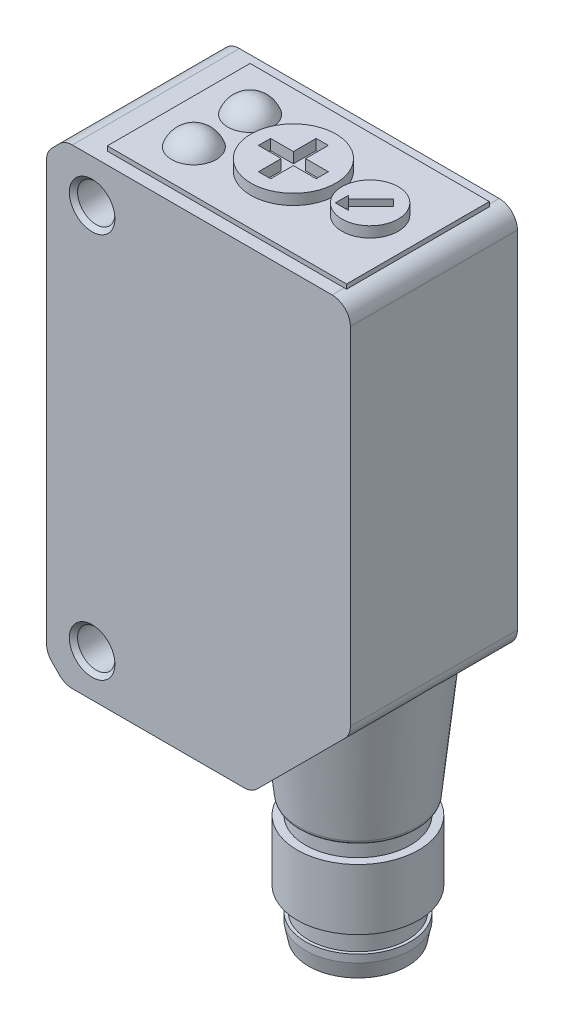
SolidWorks part; units mm, degrees
ref_plane "Front Plane" through (0, 0, 0) normal (0, 0, 1) x (1, 0, 0)
ref_plane "Top Plane" through (0, 0, 0) normal (0, 1, 0) x (1, 0, 0)
ref_plane "Right Plane" through (0, 0, 0) normal (1, 0, 0) x (0, 0, -1)
ref_plane "Plane1" through (0, 0, 0) normal (0, 0, 1) x (1, 0, 0)
sketch "Sketch1" plane through (0, 0, 0) normal (0, 0, 1) x (1, 0, 0)
  line L0 (-3, 26.5029) -> (-3, -1.1029)
  line L1 (-2.6485, -1.9515) -> (-2.1515, -2.4485)
  line L2 (-1.3029, -2.8) -> (10.0029, -2.8)
  line L3 (10.8515, -2.4485) -> (16.6485, 3.3485)
  line L4 (17, 4.1971) -> (17, 27)
  line L5 (15.8, 28.2) -> (-1.3029, 28.2)
  line L6 (-2.1515, 27.8485) -> (-2.6485, 27.3515)
  arc A0 (-3, -1.1029) -> (-2.6485, -1.9515) centre (-1.8, -1.1029) ccw
  arc A1 (-2.1515, -2.4485) -> (-1.3029, -2.8) centre (-1.3029, -1.6) ccw
  arc A2 (10.0029, -2.8) -> (10.8515, -2.4485) centre (10.0029, -1.6) ccw
  arc A3 (16.6485, 3.3485) -> (17, 4.1971) centre (15.8, 4.1971) ccw
  arc A4 (17, 27) -> (15.8, 28.2) centre (15.8, 27) ccw
  arc A5 (-1.3029, 28.2) -> (-2.1515, 27.8485) centre (-1.3029, 27) ccw
  arc A6 (-2.6485, 27.3515) -> (-3, 26.5029) centre (-1.8, 26.5029) ccw
extrude "Boss-Extrude1" add sketch "Sketch1" against normal blind 11
ref_plane "Plane2" through (0, 0, -5.5) normal (0, 0, 1) x (1, 0, 0)
sketch "Sketch2" plane through (0, 0, -5.5) normal (0, 0, 1) x (1, 0, 0)
  line L0 (12, 4.7) -> (16.8991, 4.7)
  line L1 (16.8991, 4.7) -> (15.8973, -4.8314)
  line L2 (15.599, -5.1) -> (15.45, -5.1)
  line L3 (15.45, -5.1) -> (15.45, -6.1)
  line L4 (15.45, -6.1) -> (16, -6.1)
  line L5 (16, -6.1) -> (16, -10.1)
  line L6 (16, -10.1) -> (15.25, -10.1)
  line L7 (15.25, -10.1) -> (15.25, -11.6)
  line L8 (15.25, -11.6) -> (15.45, -11.6)
  line L9 (15.45, -11.6) -> (15.45, -12.1)
  line L10 (15.45, -12.1) -> (15.25, -13.1)
  line L11 (15.25, -13.1) -> (12, -13.1)
  line L12 (12, -13.1) -> (12, 4.7)
  line L13 (12, -13.1) -> (12, 4.7) construction
  arc A0 (15.8973, -4.8314) -> (15.599, -5.1) centre (15.599, -4.8) cw
revolve "Revolve1" add sketch "Sketch2" angle 360 about L13 reverse direction yes
cosmetic thread "Cosmetic Thread1" parameters "D1"=4, "D2"=6.466
ref_plane "Plane3" through (0, -9.3, 0) normal (0, 1, 0) x (1, 0, 0)
sketch "Sketch3" plane through (0, -9.3, 0) normal (0, 1, 0) x (1, 0, 0)
  circle A0 centre (12, 5.5) radius 2.9
  circle A1 centre (13.4158, 4.4714) radius 0.5
  circle A2 centre (13.4158, 6.5286) radius 0.5
  circle A3 centre (11.4592, 3.8357) radius 0.5
  circle A4 centre (11.4592, 7.1643) radius 0.5
extrude "Cut-Extrude1" cut sketch "Sketch3" against normal blind 4
ref_plane "Plane4" through (0, 28.2, 0) normal (0, 1, 0) x (1, 0, 0)
sketch "Sketch4" plane through (0, 28.2, 0) normal (0, 1, 0) x (1, 0, 0)
  line L0 (0.2, 10.2) -> (0.2, 0.8)
  line L1 (0.2, 0.8) -> (15.95, 0.8)
  line L2 (15.95, 0.8) -> (15.95, 10.2)
  line L3 (15.95, 10.2) -> (0.2, 10.2)
  line L4 (11.6565, 4.3565) -> (12.5293, 4.3565)
  line L5 (12.5293, 4.3565) -> (12.305, 4.5808)
  line L6 (12.305, 4.5808) -> (13.7899, 6.0657)
  line L7 (13.7899, 6.0657) -> (13.3657, 6.4899)
  line L8 (13.3657, 6.4899) -> (11.8808, 5.005)
  line L9 (11.8808, 5.005) -> (11.6565, 5.2293)
  line L10 (11.6565, 5.2293) -> (11.6565, 4.3565)
  line L11 (5.85, 5.9) -> (5.85, 5.1)
  line L12 (5.85, 5.1) -> (7.35, 5.1)
  line L13 (7.35, 5.1) -> (7.35, 3.6)
  line L14 (7.35, 3.6) -> (8.15, 3.6)
  line L15 (8.15, 3.6) -> (8.15, 5.1)
  line L16 (8.15, 5.1) -> (9.65, 5.1)
  line L17 (9.65, 5.1) -> (9.65, 5.9)
  line L18 (9.65, 5.9) -> (8.15, 5.9)
  line L19 (8.15, 5.9) -> (8.15, 7.4)
  line L20 (8.15, 7.4) -> (7.35, 7.4)
  line L21 (7.35, 7.4) -> (7.35, 5.9)
  line L22 (7.35, 5.9) -> (5.85, 5.9)
extrude "Boss-Extrude2" add sketch "Sketch4" along normal blind 1
ref_plane "Plane5" through (0, 28.2, 0) normal (0, 1, 0) x (1, 0, 0)
sketch "Sketch5" plane through (0, 28.2, 0) normal (0, 1, 0) x (1, 0, 0)
  line L0 (0.2, 10.2) -> (0.2, 0.8)
  line L1 (0.2, 0.8) -> (15.95, 0.8)
  line L2 (15.95, 0.8) -> (15.95, 10.2)
  line L3 (15.95, 10.2) -> (0.2, 10.2)
  circle A0 centre (12.8, 5.5) radius 1.85
  circle A1 centre (7.75, 5.5) radius 2.8
extrude "Cut-Extrude2" cut sketch "Sketch5" along normal blind 1
ref_plane "Plane6" through (0, 28.2, 0) normal (0, 1, 0) x (1, 0, 0)
sketch "Sketch6" plane through (0, 28.2, 0) normal (0, 1, 0) x (1, 0, 0)
  line L0 (0.2, 10.2) -> (0.2, 0.8)
  line L1 (0.2, 0.8) -> (15.95, 0.8)
  line L2 (15.95, 0.8) -> (15.95, 10.2)
  line L3 (15.95, 10.2) -> (0.2, 10.2)
extrude "Boss-Extrude3" add sketch "Sketch6" along normal blind 0.3
ref_plane "Plane7" through (3.1, 0, 0) normal (1, 0, 0) x (0, 0, -1)
sketch "Sketch7" plane through (3.1, 0, 0) normal (1, 0, 0) x (0, 0, -1)
  line L0 (8.85, 28) -> (5.75, 28)
  line L1 (8.85, 28) -> (5.75, 28) construction
  arc A0 (5.75, 28) -> (8.85, 28) centre (7.3, 28) cw
revolve "Revolve2" add sketch "Sketch7" angle 360 about L1 reverse direction yes
ref_plane "Plane8" through (-2.8, 0, 0) normal (1, 0, 0) x (0, 0, -1)
sketch "Sketch8" plane through (-2.8, 0, 0) normal (1, 0, 0) x (0, 0, -1)
  line L0 (1.425, 19.925) -> (1.425, 2.675)
  line L1 (2.225, 1.875) -> (8.775, 1.875)
  line L2 (9.575, 2.675) -> (9.575, 19.925)
  line L3 (8.775, 20.725) -> (2.225, 20.725)
  arc A0 (1.425, 2.675) -> (2.225, 1.875) centre (2.225, 2.675) ccw
  arc A1 (8.775, 1.875) -> (9.575, 2.675) centre (8.775, 2.675) ccw
  arc A2 (9.575, 19.925) -> (8.775, 20.725) centre (8.775, 19.925) ccw
  arc A3 (2.225, 20.725) -> (1.425, 19.925) centre (2.225, 19.925) ccw
extrude "Cut-Extrude3" cut sketch "Sketch8" against normal blind 0.2
ref_plane "Plane9" through (0, 0, -11) normal (0, 0, 1) x (1, 0, 0)
sketch "Sketch9" plane through (0, 0, -11) normal (0, 0, 1) x (1, 0, 0)
  line L0 (4.4, 0.2) -> (9.0917, 0.2)
  line L1 (9.3745, 0.3172) -> (13.8828, 4.8255)
  line L2 (14, 5.1083) -> (14, 24.8)
  line L3 (13.6, 25.2) -> (4.4, 25.2)
  line L4 (4, 24.8) -> (4, 0.6)
  arc A0 (4, 0.6) -> (4.4, 0.2) centre (4.4, 0.6) ccw
  arc A1 (9.0917, 0.2) -> (9.3745, 0.3172) centre (9.0917, 0.6) ccw
  arc A2 (13.8828, 4.8255) -> (14, 5.1083) centre (13.6, 5.1083) ccw
  arc A3 (14, 24.8) -> (13.6, 25.2) centre (13.6, 24.8) ccw
  arc A4 (4.4, 25.2) -> (4, 24.8) centre (4.4, 24.8) ccw
extrude "Cut-Extrude4" cut sketch "Sketch9" along normal blind 0.1
ref_plane "Plane10" through (0, 0, 0) normal (1, 0, 0) x (0, 0, -1)
sketch "Sketch10" plane through (0, 0, 0) normal (1, 0, 0) x (0, 0, -1)
  line L0 (0, 0) -> (0, 1.5)
  line L1 (0, 1.5) -> (0.2705, 1.2295)
  line L2 (0.2705, 1.2295) -> (10.7295, 1.2295)
  line L3 (10.7295, 1.2295) -> (11, 1.5)
  line L4 (11, 1.5) -> (11, 0)
  line L5 (11, 0) -> (0, 0)
  line L6 (11, 0) -> (0, 0) construction
revolve "Cut-Revolve1" cut sketch "Sketch10" angle 360 about L6 reverse direction yes
cosmetic thread "Cosmetic Thread2" parameters "D1"=11, "D2"=3
ref_plane "Plane11" through (0, 0, 0) normal (1, 0, 0) x (0, 0, -1)
sketch "Sketch11" plane through (0, 0, 0) normal (1, 0, 0) x (0, 0, -1)
  line L0 (0, 25.4) -> (0, 26.9)
  line L1 (0, 26.9) -> (0.2705, 26.6295)
  line L2 (0.2705, 26.6295) -> (10.7295, 26.6295)
  line L3 (10.7295, 26.6295) -> (11, 26.9)
  line L4 (11, 26.9) -> (11, 25.4)
  line L5 (11, 25.4) -> (0, 25.4)
  line L6 (11, 25.4) -> (0, 25.4) construction
revolve "Cut-Revolve2" cut sketch "Sketch11" angle 360 about L6 reverse direction yes
cosmetic thread "Cosmetic Thread3" parameters "D1"=11, "D2"=3
ref_plane "Plane12" through (3.1, 0, 0) normal (1, 0, 0) x (0, 0, -1)
sketch "Sketch12" plane through (3.1, 0, 0) normal (1, 0, 0) x (0, 0, -1)
  line L0 (5.15, 28) -> (2.05, 28)
  line L1 (5.15, 28) -> (2.05, 28) construction
  arc A0 (2.05, 28) -> (5.15, 28) centre (3.6, 28) cw
revolve "Revolve3" add sketch "Sketch12" angle 360 about L1 reverse direction yes
